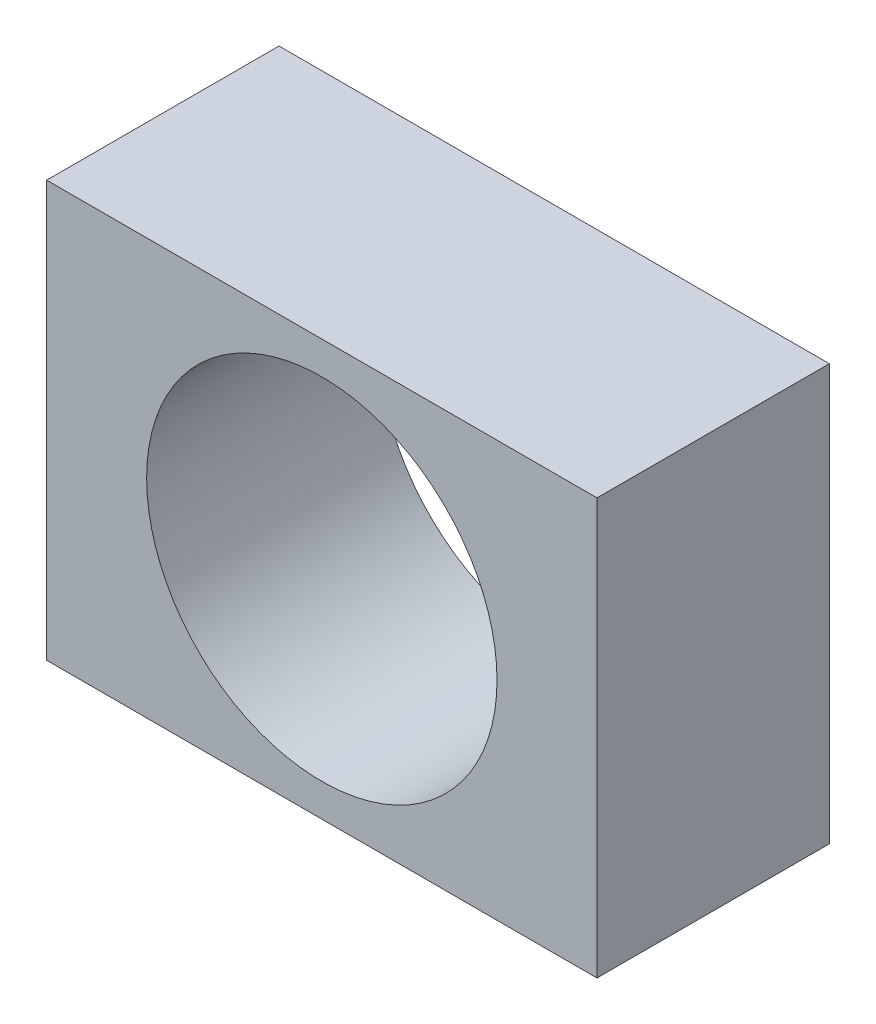
SolidWorks part; units mm, degrees
ref_plane "Front Plane" through (0, 0, 0) normal (0, 0, 1) x (1, 0, 0)
ref_plane "Top Plane" through (0, 0, 0) normal (0, 1, 0) x (1, 0, 0)
ref_plane "Right Plane" through (0, 0, 0) normal (1, 0, 0) x (0, 0, -1)
sketch "Sketch1" plane through (0, 0, 0) normal (0, 0, 1) x (1, 0, 0)
  line L1 (-45, -34) -> (45, -34)
  line L2 (-45, -34) -> (-45, 34)
  line L3 (-45, 34) -> (45, 34)
  line L4 (45, -34) -> (45, 34)
  line L5 (-45, -34) -> (45, 34) construction
  line L6 (-45, 34) -> (45, -34) construction
  circle A0 centre (0, 0) radius 28.65
  point P0 (0, 0)
  dimension "D3" = 57.3
  dimension "D1" = 90
  dimension "D2" = 68
extrude "Boss-Extrude1" add sketch "Sketch1" along normal mid plane 38
